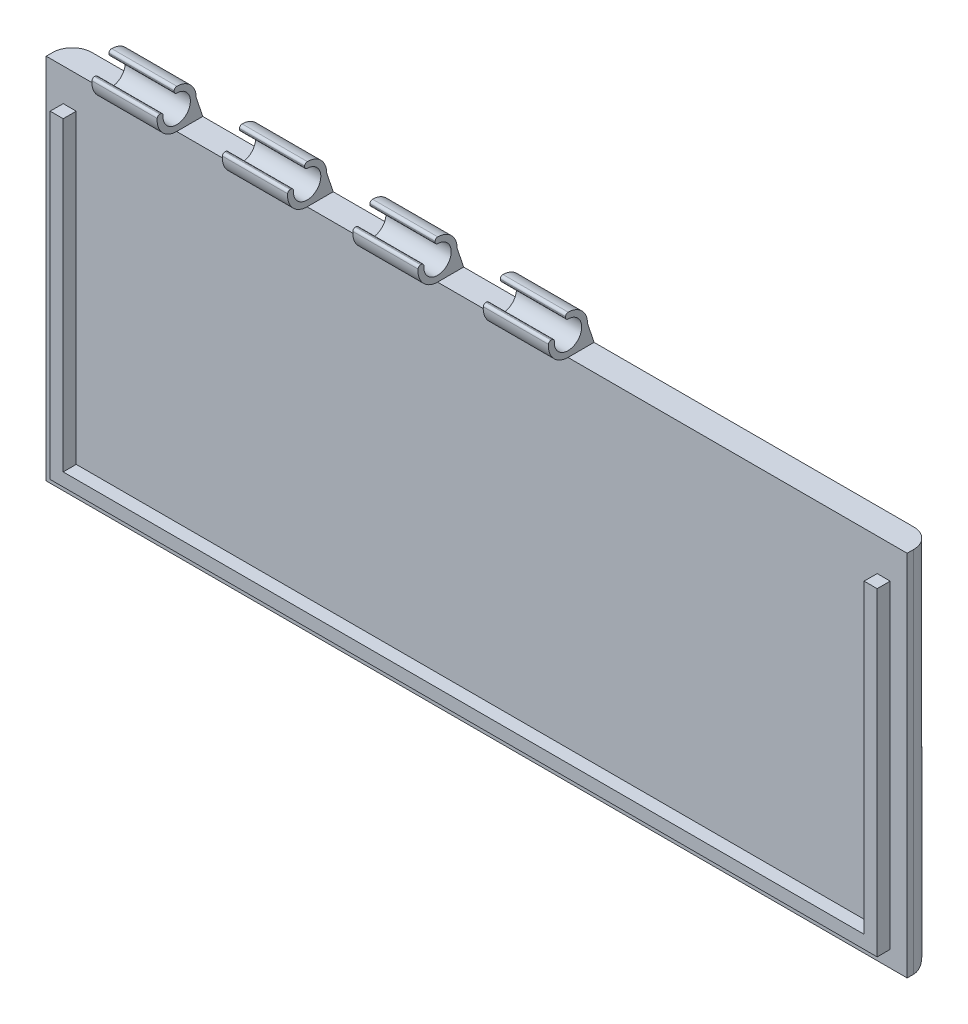
SolidWorks part; units mm, degrees
ref_plane "Front Plane" through (0, 0, 0) normal (0, 0, 1) x (1, 0, 0)
ref_plane "Top Plane" through (0, 0, 0) normal (0, 1, 0) x (1, 0, 0)
ref_plane "Right Plane" through (0, 0, 0) normal (1, 0, 0) x (0, 0, -1)
sketch "Sketch1" plane through (0, 0, 0) normal (0, 0, 1) x (1, 0, 0)
  line L1 (-33, -14.1) -> (33, -14.1)
  line L2 (-33, -14.1) -> (-33, 14.1)
  line L3 (-33, 14.1) -> (33, 14.1)
  line L4 (33, -14.1) -> (33, 14.1)
  line L5 (-33, -14.1) -> (33, 14.1) construction
  line L6 (-33, 14.1) -> (33, -14.1) construction
  point P0 (0, 0)
  dimension "D1" = 66
  dimension "D2" = 28.2
extrude "Boss-Extrude1" add sketch "Sketch1" along normal blind 2
sketch "Sketch5" plane through (-33, 0, 0) normal (-1, 0, 0) x (0, 0, 1)
  line L0 (2, 14.1) -> (2, 15.6) construction
  line L1 (0.5, 15.6) -> (0, 14.1)
  line L6 (0, 14.1) -> (0, -14.1)
  line L7 (0, -14.1) -> (2, -14.1)
  line L8 (2, -14.1) -> (2, 14.1)
  line L9 (2, 14.1) -> (0, 14.1)
  line L13 (2, 14.1) -> (0, 14.1)
  arc A0 (2, 14.1) -> (0.5, 15.6) centre (2, 15.6) ccw
  circle A1 centre (2, 15.6) radius 1.05
  dimension "D1" = 3
  dimension "D3" = 2.1
  dimension "D2" = 0
extrude "Boss-Extrude2" add sketch "Sketch5" against normal blind 5
sketch "Sketch8" plane through (-33, 0, 0) normal (-1, 0, 0) x (0, 0, 1)
  line L1 (2.189, 17.66) -> (3.9486, 17.66)
  line L2 (2.189, 17.66) -> (2.189, 15.9004)
  line L3 (2.189, 15.9004) -> (3.9486, 15.9004)
  line L4 (3.9486, 17.66) -> (3.9486, 15.9004)
  dimension "D1" = 0.189
  dimension "D2" = 1.9486
  dimension "D3" = 1.8004
extrude "Cut-Extrude3" cut sketch "Sketch8" against normal up to next (5 mm away)
fillet "Fillet4" radius 0.2 4 edges at (-30.5, 15.9004, 3.0061) (-30.5, 15.9004, 3.4696) (-30.5, 16.6329, 2.189) (-30.5, 17.088, 2.189)
pattern_linear "LPattern1" count 8 spacing 5 along (1, 0, 0) skipping (2, 0), (4, 0), (6, 0) of "Boss-Extrude2", "Cut-Extrude3", "Fillet4"
sketch "Sketch6" plane through (0, 14.1, 0) normal (0, 1, 0) x (1, 0, 0)
  line L1 (-33, 0) -> (-28, 0)
  line L2 (-33, 0) -> (-33, -7.4341)
  line L3 (-33, -7.4341) -> (-28, -7.4341)
  line L4 (-28, 0) -> (-28, -7.4341)
  dimension "D1" = 5
  dimension "D2" = 7.4341
extrude "Cut-Extrude1" cut sketch "Sketch6" along normal through all
fillet "Fillet5" radius 1.5 3 edges at (-33, 0, 0) (0, -14.1, 0) (33, 0, 0)
sketch "Sketch9" plane through (0, 0, 2) normal (0, 0, 1) x (1, 0, 0)
  line L0 (-33, 11.6) -> (-31.7, 11.6) construction
  line L1 (-33, 14.1) -> (-33, -14.1) construction
  line L2 (-31.7, -14.1) -> (-31.7, 11.6) construction
  line L3 (-33, -14.1) -> (33, -14.1) construction
  line L4 (33, 11.6) -> (31.7, 11.6) construction
  line L5 (33, -14.1) -> (33, 14.1) construction
  line L6 (31.7, -14.1) -> (31.7, -12.85) construction
  line L7 (31.7, 11.6) -> (31.7, -12.85) construction
  line L8 (31.7, -12.85) -> (-31.7, -12.85) construction
  line L9 (33, 14.1) -> (7, 14.1) construction
  line L11 (-31.7, 11.6) -> (-30.7, 11.6)
  line L12 (-31.7, 11.6) -> (-31.7, -12.85)
  line L13 (-31.7, -12.85) -> (-30.7, -12.85)
  line L14 (-30.7, 11.6) -> (-30.7, -11.85)
  line L15 (-30.7, -11.85) -> (30.7, -11.85)
  line L17 (-30.7, -12.85) -> (31.7, -12.85)
  line L18 (31.7, -11.85) -> (31.7, -12.85)
  line L19 (31.7, 11.6) -> (30.7, 11.6)
  line L20 (31.7, 11.6) -> (31.7, -11.85)
  line L22 (30.7, 11.6) -> (30.7, -11.85)
  dimension "D1" = 1.3
  dimension "D2" = 1.3
  dimension "D3" = 1.25
  dimension "D4" = 2.5
  dimension "D5" = 2.5
  dimension "D6" = 1
  dimension "D7" = 1
  dimension "D8" = 1
  dimension "D9" = 1
extrude "Boss-Extrude3" add sketch "Sketch9" along normal blind 1
